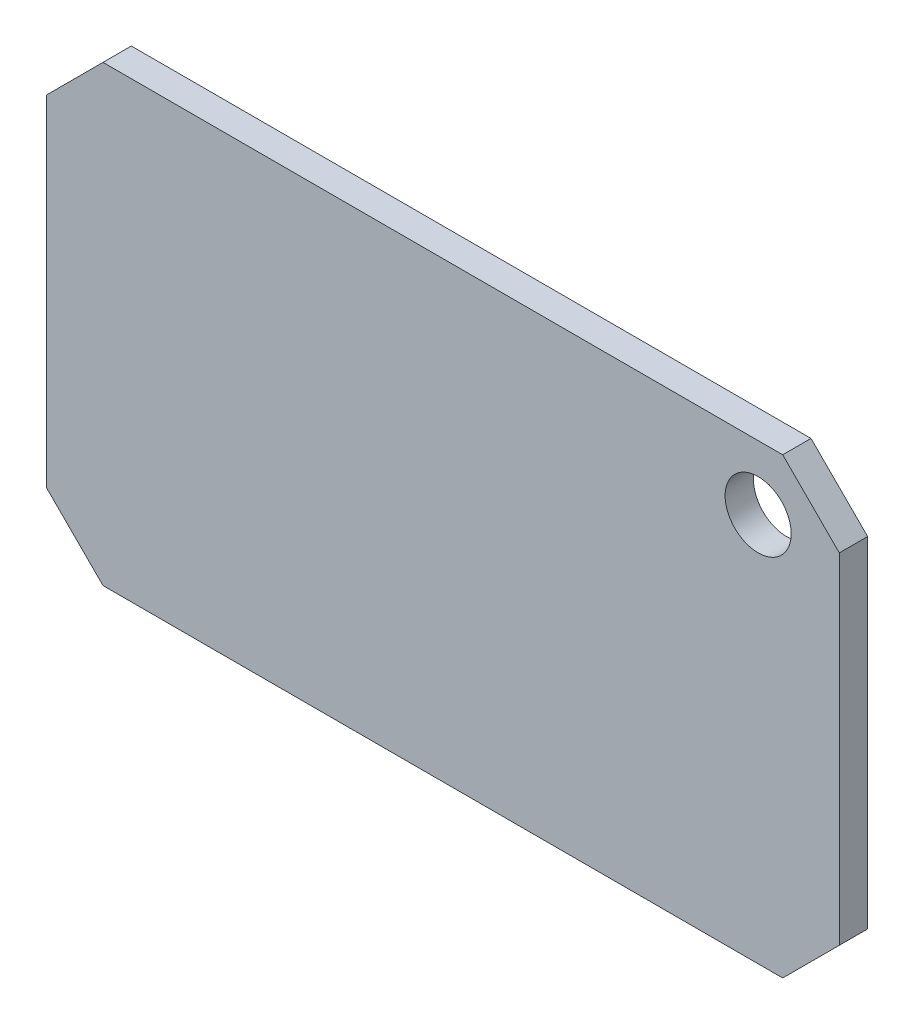
SolidWorks part; units mm, degrees
ref_plane "Front Plane" through (0, 0, 0) normal (0, 0, 1) x (1, 0, 0)
ref_plane "Top Plane" through (0, 0, 0) normal (0, 1, 0) x (1, 0, 0)
ref_plane "Right Plane" through (0, 0, 0) normal (1, 0, 0) x (0, 0, -1)
sketch "Sketch1" plane through (0, 0, 0) normal (0, 0, 1) x (1, 0, 0)
  line L0 (0, 0) -> (0, 12) construction
  line L1 (0, 0) -> (-21, 0) construction
  line L5 (-21, 9) -> (-18, 12)
  line L6 (-18, 12) -> (18, 12)
  line L7 (18, 12) -> (21, 9)
  line L8 (21, 9) -> (21, -9)
  line L9 (21, -9) -> (18, -12)
  line L10 (18, -12) -> (-18, -12)
  line L11 (-18, -12) -> (-21, -9)
  line L12 (-21, -9) -> (-21, 9)
  line L15 (18, 12) -> (18, -12) construction
  line L16 (-18, 12) -> (-18, -12) construction
  line L17 (-21, -9) -> (21, -9) construction
  line L18 (21, 9) -> (-21, 9) construction
  line L19 (0, 0) -> (21, 0) construction
  circle A0 centre (16.7, 8.6) radius 1.75
  point P5 (-21, 9)
  point P6 (-21, 8.6)
  point P15 (-21, 0)
  point P18 (-18.8029, 0)
  point P19 (-20.2284, -5.369)
  dimension "D9" = 3.5
  dimension "D1" = 45
  dimension "D3" = 24
  dimension "D5" = 42
  dimension "D6" = 3
  dimension "D7" = 4.3
  dimension "D8" = 3.4
extrude "Boss-Extrude1" add sketch "Sketch1" along normal blind 1.5
